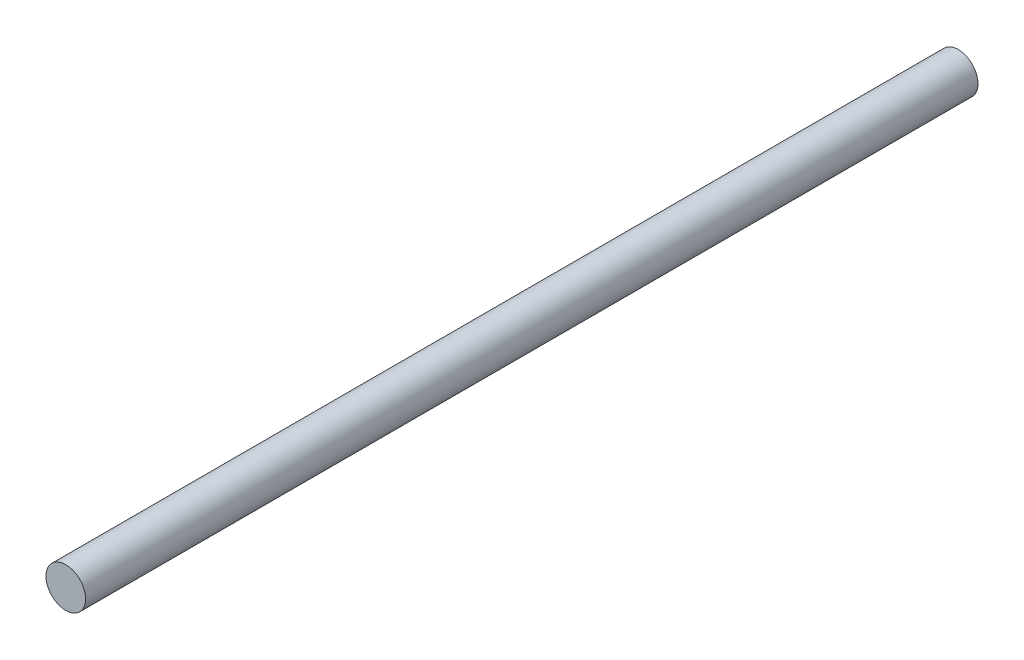
SolidWorks part; units mm, degrees
ref_plane "Front Plane" through (0, 0, 0) normal (0, 0, 1) x (1, 0, 0)
ref_plane "Top Plane" through (0, 0, 0) normal (0, 1, 0) x (1, 0, 0)
ref_plane "Right Plane" through (0, 0, 0) normal (1, 0, 0) x (0, 0, -1)
sketch "Sketch1" plane through (0, 0, 0) normal (0, 0, 1) x (1, 0, 0)
  circle A0 centre (0, 0) radius 6
  dimension "D1" = 12
extrude "Boss-Extrude1" add sketch "Sketch1" along normal mid plane 270
